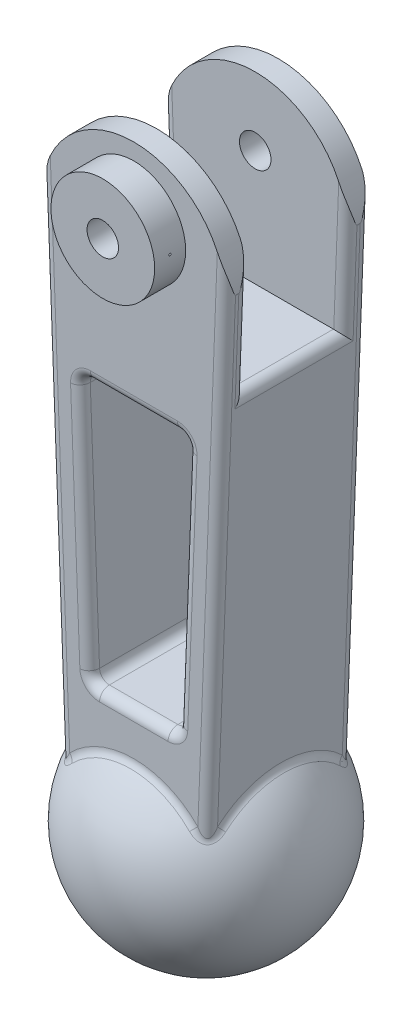
SolidWorks part; units mm, degrees
material "ABS PC"
ref_plane "Front Plane" through (0, 0, 0) normal (0, 0, 1) x (1, 0, 0)
ref_plane "Top Plane" through (0, 0, 0) normal (0, 1, 0) x (1, 0, 0)
ref_plane "Right Plane" through (0, 0, 0) normal (1, 0, 0) x (0, 0, -1)
sketch "Sketch1" plane through (0, 0, 0) normal (0, 0, 1) x (1, 0, 0)
  line L0 (0, 21.59) -> (0, -21.59) construction
  line L1 (0, 21.59) -> (0, -21.59)
  arc A0 (0, -21.59) -> (0, 21.59) centre (0, 0) ccw
  dimension "D1" = 43.18
revolve "Revolve4" add sketch "Sketch1" angle 360 about L0
sketch "Sketch3" plane through (0, 0, 0) normal (0, 0, 1) x (1, 0, 0)
  line L0 (0, 0) -> (0, 102.87) construction
  line L3 (-13.843, 0) -> (13.843, 0)
  line L8 (13.843, 0) -> (17.78, 102.87)
  line L9 (-13.843, 0) -> (-17.78, 102.87)
  arc A0 (17.78, 102.87) -> (-17.78, 102.87) centre (0, 102.87) ccw
  point P6 (0, 102.87)
  point P11 (0, 102.87)
  dimension "D3" = 92.192
  dimension "D5" = 17.78
  dimension "D1" = 102.87
  dimension "D2" = 35.56
  dimension "D4" = 27.686
  dimension "D6" = 92.192
extrude "Boss-Extrude1" add sketch "Sketch3" along normal mid plane 27.94 contours L0 | L0 | L8 A0 L9 L3
sketch "Sketch4" plane through (0, 0, 13.97) normal (0, 0, 1) x (1, 0, 0)
  line L0 (0, 102.87) -> (0, 107.442)
  circle A0 centre (0, 107.442) radius 3.048
  dimension "D2" = 6.096
  dimension "D1" = 4.572
extrude "Cut-Extrude2" cut sketch "Sketch4" against normal through all contours A0 region at (2.0943, 105.3477, 13.97)
ref_plane "Plane1" through (0, 0, 0) normal (0, 0, 1) x (1, 0, 0)
sketch "Sketch6" plane through (0, 0, 0) normal (0, 0, 1) x (1, 0, 0)
  line L0 (-17.0995, 85.09) -> (17.0995, 85.09)
  line L1 (14.164, 8.3874) -> (17.78, 102.87) construction
  line L2 (-14.164, 8.3874) -> (-17.78, 102.87) construction
  line L3 (-17.78, 102.87) -> (17.78, 102.87) construction
  line L4 (-17.78, 102.87) -> (-17.0995, 85.09)
  line L5 (17.78, 102.87) -> (17.0995, 85.09)
  arc A2 (17.78, 102.87) -> (-17.78, 102.87) centre (0, 102.87) ccw
  point P5 (0, 102.87)
  point P11 (0, 85.09)
  dimension "D1" = 17.78
extrude "Cut-Extrude4" cut sketch "Sketch6" against normal mid plane 19.05 contours L5 L0 L4 A2
sketch "Sketch7" plane through (0, 0, 13.97) normal (0, 0, 1) x (1, 0, 0)
  line L7 (-7.8186, 8.6302) -> (-11.4346, 103.1128)
  line L8 (-8.4604, 25.4) -> (-10.4046, 76.2)
  line L9 (-8.4604, 25.4) -> (8.4604, 25.4)
  line L10 (7.8186, 8.6302) -> (11.4346, 103.1128)
  line L11 (8.4604, 25.4) -> (10.4046, 76.2)
  line L12 (-10.4046, 76.2) -> (10.4046, 76.2)
  dimension "D3" = 25.4
  dimension "D4" = 50.8
  dimension "D1" = 6.35
  dimension "D2" = 6.35
extrude "Cut-Extrude5" cut sketch "Sketch7" against normal through all
fillet "Fillet1" radius 1.905 30 edges at (0, 25.4, -13.97) (0, 76.2, -13.97) (0, 76.2, 13.97) (0, 25.4, 13.97) (-17.4398, 93.98, 9.525) (-17.78, 102.87, 11.7475) (-15.972, 55.6287, 13.97) (-15.972, 55.6287, -13.97) (-17.78, 102.87, -11.7475) (-17.4398, 93.98, -9.525) (-17.0995, 85.09, 0) (9.4325, 50.8, -13.97) (10.4046, 76.2, 0) (9.4325, 50.8, 13.97) (8.4604, 25.4, 0) (17.0995, 85.09, 0) (-9.4325, 50.8, -13.97) (-8.4604, 25.4, 0) (-9.4325, 50.8, 13.97) (-10.4046, 76.2, 0) (17.78, 102.87, -11.7475) (15.972, 55.6287, -13.97) (15.972, 55.6287, 13.97) (17.78, 102.87, 11.7475) (17.4398, 93.98, 9.525) (17.4398, 93.98, -9.525) (0, 16.4611, 13.97) (0, 16.4611, -13.97) (14.4567, 16.0353, 0) (-14.4567, 16.0353, 0)
sketch "Sketch8" plane through (0, 0, 13.97) normal (0, 0, 1) x (1, 0, 0)
  circle A0 centre (0, 107.442) radius 10.0335
  circle A1 centre (0, 107.442) radius 3.048 construction
  circle A2 centre (0, 107.442) radius 3.048
extrude "Boss-Extrude2" add sketch "Sketch8" along normal blind 6
ref_plane "Plane2" through (-5.9202, -0.2266, 0) normal (-0.9993, -0.0382, 0) x (0, 0, 1)
sketch "Sketch10" plane through (-5.9202, -0.2266, 0) normal (-0.9993, -0.0382, 0) x (0, 0, 1)
  line L0 (19.97, 97.3299) -> (19.97, 117.3969) construction
  circle A0 centre (16.97, 107.8211) radius 0.2
  point P0 (16.97, 107.8211)
  dimension "D1" = 3
extrude "Cut-Extrude6" cut sketch "Sketch10" against normal through all
